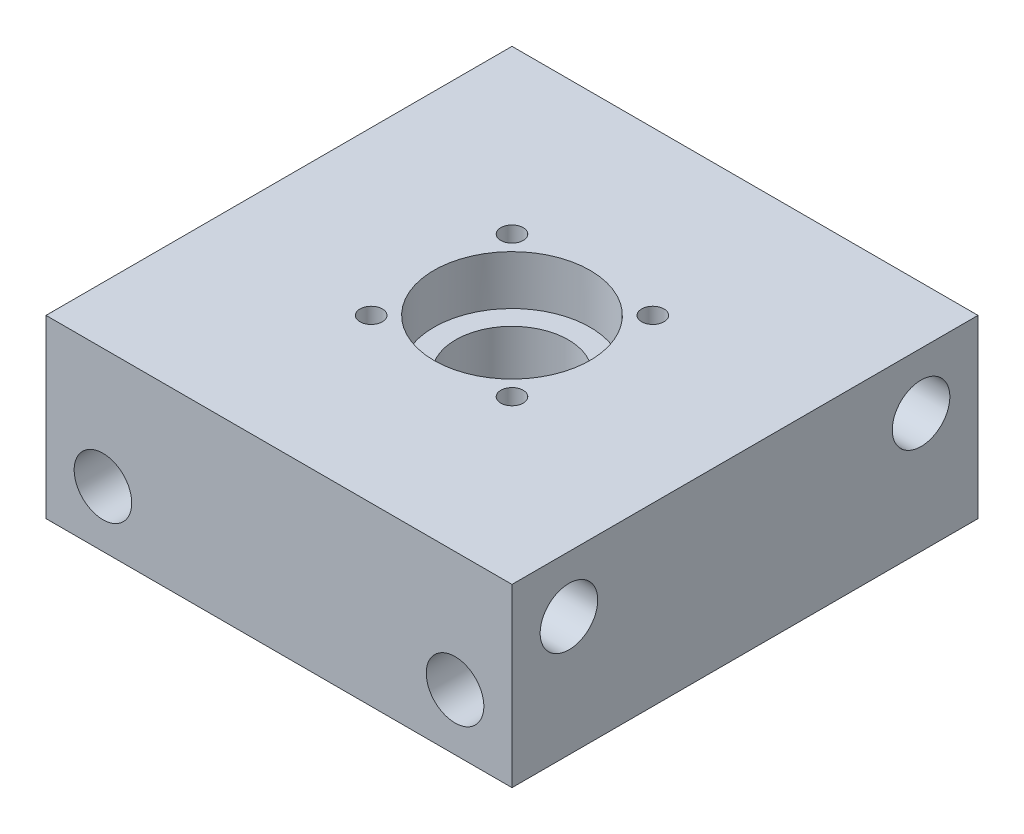
SolidWorks part; units mm, degrees
material "ABS"
ref_plane "Front Plane" through (0, 0, 0) normal (0, 0, 1) x (1, 0, 0)
ref_plane "Top Plane" through (0, 0, 0) normal (0, 1, 0) x (1, 0, 0)
ref_plane "Right Plane" through (0, 0, 0) normal (1, 0, 0) x (0, 0, -1)
sketch "Sketch1" plane through (0, 0, 0) normal (0, 1, 0) x (1, 0, 0)
  line L0 (-25, 94.322) -> (-25, -161.1056) construction
  line L1 (0, 212.1837) -> (0, -209.6879) construction
  line L2 (-178.557, 25) -> (189.3494, 25) construction
  line L3 (-284.8586, 0) -> (271.277, 0) construction
  line L4 (-33.0875, 29.0875) -> (33.0875, 29.0875)
  line L5 (-29.0875, 33.0875) -> (-20.9125, 33.0875)
  line L6 (-29.0875, 33.0875) -> (-29.0875, -33.0875)
  line L7 (-29.0875, -33.0875) -> (-20.9125, -33.0875)
  line L8 (-20.9125, 33.0875) -> (-20.9125, -33.0875)
  line L9 (-33.0875, 20.9125) -> (33.0875, 20.9125)
  line L10 (-33.0875, -29.0875) -> (-33.0875, -20.9125)
  line L11 (-178.557, -25) -> (189.3494, -25) construction
  line L12 (33.0875, -29.0875) -> (33.0875, -20.9125)
  line L13 (-33.0875, 29.0875) -> (33.0875, 29.0875)
  line L14 (-33.0875, 29.0875) -> (-33.0875, 20.9125)
  line L15 (-33.0875, 20.9125) -> (33.0875, 20.9125)
  line L16 (33.0875, 29.0875) -> (33.0875, 20.9125)
  line L17 (-33.0875, -20.9125) -> (33.0875, -20.9125)
  line L18 (-33.0875, -29.0875) -> (33.0875, -29.0875)
  line L19 (-33.0875, -20.9125) -> (33.0875, -20.9125)
  line L20 (-33.0875, -29.0875) -> (33.0875, -29.0875)
  line L21 (29.0875, -33.0875) -> (20.9125, -33.0875)
  line L22 (29.0875, 33.0875) -> (20.9125, 33.0875)
  line L23 (25, 94.322) -> (25, -161.1056) construction
  line L24 (20.9125, 33.0875) -> (20.9125, -33.0875)
  line L25 (29.0875, 33.0875) -> (29.0875, -33.0875)
  line L26 (13.2765, 10) -> (11.6382, 12.8375)
  line L27 (-33.0875, 33.0875) -> (33.0875, 33.0875)
  line L28 (-33.0875, 33.0875) -> (-33.0875, -33.0875)
  line L29 (-33.0875, -33.0875) -> (33.0875, -33.0875)
  line L30 (33.0875, 33.0875) -> (33.0875, -33.0875)
  line L31 (-6.7235, 10) -> (-8.3618, 12.8375)
  line L32 (-8.3618, 12.8375) -> (-11.6382, 12.8375)
  line L33 (-11.6382, 12.8375) -> (-13.2765, 10)
  line L34 (-13.2765, 10) -> (-11.6382, 7.1625)
  line L35 (-11.6382, 7.1625) -> (-8.3618, 7.1625)
  line L36 (-8.3618, 7.1625) -> (-6.7235, 10)
  line L37 (11.6382, 12.8375) -> (8.3618, 12.8375)
  line L38 (8.3618, 12.8375) -> (6.7235, 10)
  line L39 (6.7235, 10) -> (8.3618, 7.1625)
  line L40 (8.3618, 7.1625) -> (11.6382, 7.1625)
  line L41 (11.6382, 7.1625) -> (13.2765, 10)
  line L42 (13.2765, -10) -> (11.6382, -7.1625)
  line L43 (11.6382, -7.1625) -> (8.3618, -7.1625)
  line L44 (8.3618, -7.1625) -> (6.7235, -10)
  line L45 (6.7235, -10) -> (8.3618, -12.8375)
  line L46 (8.3618, -12.8375) -> (11.6382, -12.8375)
  line L47 (11.6382, -12.8375) -> (13.2765, -10)
  line L48 (-6.7235, -10) -> (-8.3618, -7.1625)
  line L49 (-8.3618, -7.1625) -> (-11.6382, -7.1625)
  line L50 (-11.6382, -7.1625) -> (-13.2765, -10)
  line L51 (-13.2765, -10) -> (-11.6382, -12.8375)
  line L52 (-11.6382, -12.8375) -> (-8.3618, -12.8375)
  line L53 (-8.3618, -12.8375) -> (-6.7235, -10)
  circle A0 centre (0, 0) radius 11.0875
  circle A1 centre (0, 0) radius 8
  circle A2 centre (-10, 10) radius 1.5875
  circle A3 centre (10, 10) radius 1.5875
  circle A4 centre (10, 10) radius 2.8375 construction
  circle A5 centre (10, -10) radius 1.5875
  circle A6 centre (-10, 10) radius 2.8375 construction
  circle A7 centre (10, -10) radius 2.8375 construction
  circle A8 centre (-10, -10) radius 1.5875
  circle A9 centre (-10, -10) radius 2.8375 construction
  dimension "D5" = 2
  dimension "D6" = 2
  dimension "D7" = 3.175
  dimension "D14" = 5.675
  dimension "D10" = 22.175
  dimension "D11" = 16
  dimension "D2" = 25
  dimension "D3" = 25
  dimension "D4" = 4
  dimension "D8" = 10
  dimension "D9" = 10
  dimension "D12" = 8.175
  dimension "D13" = 4
extrude "Boss-Extrude1" add sketch "Sketch1" along normal blind 25 contours L24 L9 L8 L17 A3 A2 A0 | L24 L4 L8 L9 | L6 L9 L8 L4 | L27 L8 L4 L24 | L8 L5 L6 L4 | L27 L28 L4 L6 | L4 L14 L9 L6 | L9 L28 L17 L6 | L6 L17 L8 L9 | L6 L18 L8 L17 | L10 L18 L6 L17 | L28 L29 L6 L18 | L18 L6 L7 L8 | L24 L17 L8 L18 | L8 L29 L24 L18 | L25 L20 L24 L21 | L25 L19 L24 L20 | L17 L25 L18 L12 | L30 L18 L25 L29 | L25 L15 L24 L19 | L30 L9 L25 L17 | L25 L13 L24 L15 | L4 L25 L9 L16 | L25 L22 L24 L13 | L30 L27 L25 L4 | L35 L36 L31 L32 L33 L34 A2 | L40 L41 L26 L37 L38 L39 A3 | L46 L47 L42 L43 L44 L45 A5 | L52 L53 L48 L49 L50 L51 A8 region at (-31.0875, 0, -31.0875) region at (-31.0875, 0, -25) region at (-25, 0, -31.0875) region at (-25, 0, -25) region at (-31.0875, 0, 0) region at (0, 0, -31.0875) region at (0, 0, -25) region at (-25, 0, 0) region at (-31.0875, 0, 25) region at (25, 0, -31.0875) region at (25, 0, -25) region at (0, 0, -20.321) region at (-25, 0, 25) region at (-31.0875, 0, 31.0875) region at (31.0875, 0, -31.0875) region at (31.0875, 0, -25) region at (25, 0, 0) region at (0, 0, 25) region at (-25, 0, 31.0875) region at (31.0875, 0, 0) region at (25, 0, 25) region at (0, 0, 31.0875) region at (31.0875, 0, 25) region at (25, 0, 31.0875) region at (31.0875, 0, 31.0875) region at (12.3823, 0, -8.6246) region at (10.0509, 0, 7.2492) region at (-8.3828, 0, -7.3886) region at (-7.5211, 0, 8.7919)
extrude "Boss-Extrude2" add sketch "Sketch1<4>" along normal blind 18 contours A0 A1 region at (10.1164, 0, -3.7061)
sketch "Sketch1<4>" plane through (0, 0, 0) normal (0, 1, 0) x (1, 0, 0) same geometry as "Sketch1"
sketch "Sketch2" plane through (-33.0875, 0, 0) normal (-1, 0, 0) x (0, 0, 1)
  line L0 (0, 0) -> (0, 25) construction
  line L1 (-33.0875, 25) -> (33.0875, 25) construction
  circle A0 centre (-25, 17) radius 4.0875
  circle A1 centre (25, 17) radius 4.0875
  dimension "D3" = 8.175
  dimension "D1" = 25
  dimension "D2" = 8
extrude "Cut-Extrude1" cut sketch "Sketch2" against normal through all
sketch "Sketch3" plane through (0, 0, -33.0875) normal (0, 0, -1) x (-1, 0, 0)
  line L0 (0, 0) -> (0, 25) construction
  line L1 (33.0875, 25) -> (-33.0875, 25) construction
  line L2 (33.0875, 0) -> (-33.0875, 0) construction
  circle A0 centre (-25, 8) radius 4.0875
  circle A1 centre (25, 8) radius 4.0875
  dimension "D1" = 8.175
  dimension "D2" = 25
  dimension "D3" = 8
extrude "Cut-Extrude2" cut sketch "Sketch3" against normal through all
extrude "Cut-Extrude3" cut sketch "Sketch1<5>" along normal blind 16.833 contours L52 L53 L48 L49 L50 L51 A8 | L35 L36 L31 L32 L33 L34 A2 | L40 L41 L26 L37 L38 L39 A3 | L46 L47 L42 L43 L44 L45 A5 region at (12.3823, 0, -8.6246) region at (10.0509, 0, 7.2492) region at (-8.3828, 0, -7.3886) region at (-7.5211, 0, 8.7919)
sketch "Sketch1<5>" plane through (0, 0, 0) normal (0, 1, 0) x (1, 0, 0) same geometry as "Sketch1"
ref_axis "X Axis" through (36.3962, 0, 0) along (-1, 0, 0)
ref_axis "Y Axis" through (0, 0, -36.3962) along (0, 0, 1)
equation "\"rod_diameter\"= 8"
equation "\"rod_hole_thickness\"= 4"
equation "\"rod_radius\"= \"rod_diameter\" / 2"
equation "\"platter_diameter\"= 320"
equation "\"platter_radius\"= \"platter_diameter\" / 2"
equation "\"extruder_mount_hole_spacing\"= 75"
equation "\"arm_rod_spacing\"= 40"
equation "\"top_frame_rod_spacing\"= \"arm_rod_spacing\" + 40"
equation "\"motor_level_rod_spacing\"= 15"
equation "\"linear_bearing_diameter\"= 15"
equation "\"z_rod_spacing\"= 75"
equation "\"platter_rod_spacing\"= 50"
equation "\"rod_nut_thickness\"= 6.5"
equation "\"rod_nut_inscribed_diameter\"= 13"
equation "\"D2@Sketch1\"=\"platter_rod_spacing\"/2"
equation "\"D3@Sketch1\"=\"platter_rod_spacing\"/2"
equation "\"D12@Sketch1\"=\"rod_diameter\"+\"printed_hole_tolerance\""
equation "\"D4@Sketch1\"=\"rod_hole_thickness\""
equation "\"D13@Sketch1\"=\"rod_hole_thickness\""
equation "\"D1@Boss-Extrude1\"= \"rod_diameter\" * 2 + \"rod_hole_thickness\" * 2 + 1"
equation "\"D1@Boss-Extrude2\"= \"D1@Boss-Extrude1\" - 7"
equation "\"D1@Sketch2\"=\"platter_rod_spacing\"/2"
equation "\"D2@Sketch2\"=\"rod_radius\"+\"rod_hole_thickness\""
equation "\"D3@Sketch2\"=\"rod_diameter\"+\"printed_hole_tolerance\""
equation "\"D1@Sketch3\"=\"rod_diameter\"+\"printed_hole_tolerance\""
equation "\"D2@Sketch3\"=\"platter_rod_spacing\"/2"
equation "\"D3@Sketch3\"=\"rod_radius\"+\"rod_hole_thickness\""
equation "\"top_frame_spacing\"= 100"
equation "\"z_drive_rod_offset\"= 12"
equation "\"z_height\"= 400"
equation "\"gear_pitch\"=2"
equation "\"r_gear_teeth\"= 450"
equation "\"theta_gear_teeth\"= 385"
equation "\"sheet_thickness\"=5.333"
equation "\"sheet_tab_hole_thickness\"= \"sheet_thickness\""
equation "\"sheet_tab_width\"= \"sheet_thickness\"*2"
equation "\"sheet_double_tab_width\"= 35"
equation "\"sheet_bolt_diameter\"= 3"
equation "\"sheet_bolt_length\"= 16"
equation "\"sheet_nut_diameter\"= 5.5"
equation "\"sheet_nut_thickness\"= 2.5"
equation "\"sheet_nut_depth\"= 10"
equation "\"bearing_outside_diameter\"= 22"
equation "\"bearing_thickness\"= 7"
equation "\"corner_part_thickness\"= \"sheet_thickness\" + \"bearing_thickness\""
equation "\"setscrew_nut_diameter\"= 6"
equation "\"setscrew_nut_thickness\"= 3"
equation "\"setscrew_bolt_diameter\"= 3"
equation "\"motor_shaft_diameter\"= 5.7"
equation "\"D1@Cut-Extrude3\"= \"D1@Boss-Extrude1\" - \"sheet_bolt_length\" + \"sheet_nut_thickness\" + \"sheet_thickness\""
equation "\"printed_hole_tolerance\"= 0.175"
equation "\"D7@Sketch1\"=\"sheet_bolt_diameter\"+\"printed_hole_tolerance\""
equation "\"D14@Sketch1\"=\"sheet_nut_diameter\"+\"printed_hole_tolerance\""
equation "\"D10@Sketch1\"=\"bearing_outside_diameter\"+\"printed_hole_tolerance\""
